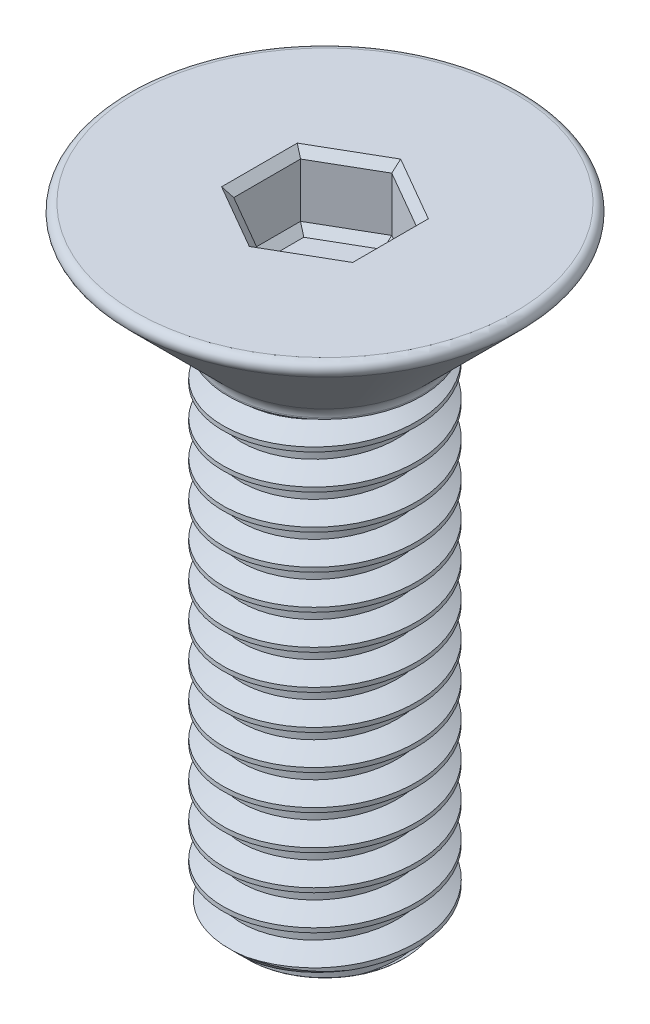
SolidWorks part; units mm, degrees
material "AISI Type A2 Tool Steel"
ref_plane "Front Plane" through (0, 0, 0) normal (0, 0, 1) x (1, 0, 0)
ref_plane "Top Plane" through (0, 0, 0) normal (0, 1, 0) x (1, 0, 0)
ref_plane "Right Plane" through (0, 0, 0) normal (1, 0, 0) x (0, 0, -1)
sketch "Sketch1" plane through (0, 0, 0) normal (0, 1, 0) x (1, 0, 0)
  circle A0 centre (0, 0) radius 1.25
  dimension "D1" = 2.5
extrude "Boss-Extrude1" add sketch "Sketch1" along normal blind 6.45
thread "Thread1" pitch 0.45 start angle 0, offset 1, length 0, pitch 0.45, diameter 2.5
ref_plane "Plane1" through (1.25, -1, 0) normal (0, 0, 1) x (1, 0, 0)
sketch "Thread Profile1" plane through (1.25, -1, 0) normal (0, 0, 1) x (1, 0, 0)
  line L0 (0, 0) -> (0, 0.45) construction
  line L11 (0, 0) -> (0, 0.3937)
  line L12 (0, 0.3937) -> (-0.2436, 0.2531)
  line L13 (-0.2436, 0.2531) -> (-0.2436, 0.1406)
  line L15 (-0.2436, 0.1406) -> (0, 0)
  line L17 (-0.2436, 0.1969) -> (0, 0.1969) construction
  point P2 (0, 0)
  dimension "Pitch" = 0.45
  dimension "Profile_Angle" = 60
  dimension "Profile_Land" = 0.1125
  dimension "Profile_Height" = 0.2436
sketch "Sketch5" plane through (0, 6.45, 0) normal (0, 1, 0) x (1, 0, 0)
  circle A0 centre (0, 0) radius 1.25
  dimension "D1" = 2.5
extrude "Boss-Extrude2" add sketch "Sketch5" along normal blind 0.1
sketch "Sketch6" plane through (0, 6.55, 0) normal (0, 1, 0) x (1, 0, 0)
  circle A0 centre (0, 0) radius 1.25
  dimension "D1" = 2.5
extrude "Boss-Extrude3" add sketch "Sketch6" along normal blind 1.45 draft 45 draft outward yes
fillet "Fillet1" radius 0.2 1 edges at (0, 6.55, 1.25)
fillet "Fillet2" radius 0.1 1 edges at (0, 8, 2.7)
sketch "Sketch7" plane through (0, 0, 0) normal (0, 0, 1) x (1, 0, 0)
  line L0 (0, 0) -> (0, 0.3237) construction
  line L1 (0, 0) -> (1.26, 0) construction
  line L2 (1.26, 0) -> (1.26, 0.26)
  line L3 (1.26, 0.26) -> (1, 0)
  line L4 (1, 0) -> (1.26, 0)
  dimension "D1" = 45
  dimension "D2" = 0.26
  dimension "D3" = 1.26
revolve "Cut-Revolve1" cut sketch "Sketch7" angle 360 about L0
sketch "Sketch8" plane through (0, 8, 0) normal (0, 1, 0) x (1, 0, 0)
  line L1 (0, 0.866) -> (-0.75, 0.433)
  line L2 (-0.75, 0.433) -> (-0.75, -0.433)
  line L3 (-0.75, -0.433) -> (0, -0.866)
  line L4 (0, -0.866) -> (0.75, -0.433)
  line L5 (0.75, -0.433) -> (0.75, 0.433)
  line L6 (0.75, 0.433) -> (0, 0.866)
  circle A0 centre (0, 0) radius 0.75 construction
  dimension "D1" = 1.5
extrude "Cut-Extrude1" cut sketch "Sketch8" against normal blind 0.8
chamfer "Chamfer1" distance 0.1 angle 45 6 edges at (-0.75, 8, 0) (-0.375, 8, 0.6495) (0.375, 8, 0.6495) (0.75, 8, 0) (0.375, 8, -0.6495) (-0.375, 8, -0.6495)
sketch "Sketch9" plane through (0, 7.2, 0) normal (0, 1, 0) x (1, 0, 0)
  line L1 (0, 0.866) -> (-0.75, 0.433)
  line L2 (-0.75, 0.433) -> (-0.75, -0.433)
  line L3 (-0.75, -0.433) -> (0, -0.866)
  line L4 (0, -0.866) -> (0.75, -0.433)
  line L5 (0.75, -0.433) -> (0.75, 0.433)
  line L6 (0.75, 0.433) -> (0, 0.866)
  circle A0 centre (0, 0) radius 0.75 construction
extrude "Cut-Extrude2" cut sketch "Sketch9" against normal blind 0.1 draft 45
